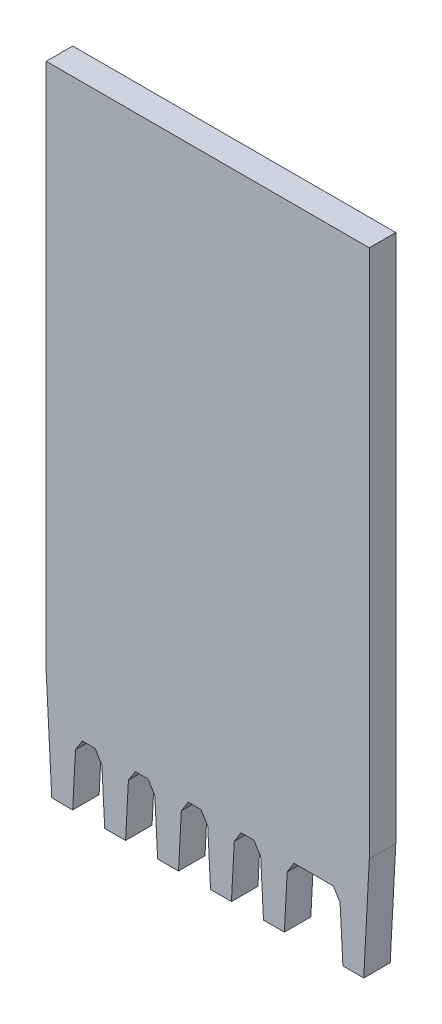
SolidWorks part; units mm, degrees
ref_plane "Front Plane" through (0, 0, 0) normal (0, 0, 1) x (1, 0, 0)
ref_plane "Top Plane" through (0, 0, 0) normal (0, 1, 0) x (1, 0, 0)
ref_plane "Right Plane" through (0, 0, 0) normal (1, 0, 0) x (0, 0, -1)
sketch "Sketch1" plane through (0, 0, 0) normal (0, 0, 1) x (1, 0, 0)
  line L0 (0, 0) -> (0, 36) construction
  line L1 (0, 36) -> (18.3124, 36) construction
  line L2 (18.3124, 36) -> (18.3124, 0) construction
  line L3 (18.3124, 0) -> (0, 0) construction
  line L4 (0, 3) -> (18.3124, 3) construction
  line L5 (0, 6) -> (18.3124, 6) construction
  line L6 (0.9062, 6) -> (0.9062, 0) construction
  line L7 (3.9062, 6) -> (3.9062, 0) construction
  line L8 (6.9062, 6) -> (6.9062, 0) construction
  line L9 (9.9062, 6) -> (9.9062, 0) construction
  line L10 (12.9062, 6) -> (12.9062, 0) construction
  line L11 (17.4062, 6) -> (17.4062, 0) construction
  line L12 (0.9062, 3) -> (3.9062, 3) construction
  line L13 (3.9062, 3) -> (6.9062, 3) construction
  line L14 (6.9062, 3) -> (9.9062, 3) construction
  line L15 (9.9062, 3) -> (12.9062, 3) construction
  line L16 (12.9062, 3) -> (17.4062, 3) construction
  line L17 (0.9062, 3) -> (0, 3) construction
  line L18 (17.4062, 3) -> (18.3124, 3) construction
  line L19 (2.4062, 3) -> (2.4062, 0) construction
  line L20 (5.4062, 3) -> (5.4062, 0) construction
  line L21 (8.4062, 3) -> (8.4062, 0) construction
  line L22 (11.4062, 3) -> (11.4062, 0) construction
  line L23 (15.1562, 3) -> (15.1562, 0) construction
  line L24 (14.4062, 3.75) -> (15.9062, 3.75) construction
  line L25 (0, 6) -> (0.3144, 0)
  line L26 (0.3144, 0) -> (1.4979, 0)
  line L27 (1.4979, 0) -> (1.6572, 3.0393)
  line L28 (3.1552, 3.0393) -> (3.3144, 0)
  line L29 (3.3144, 0) -> (4.4979, 0)
  line L30 (4.4979, 0) -> (4.6572, 3.0393)
  line L31 (6.1552, 3.0393) -> (6.3144, 0)
  line L32 (6.3144, 0) -> (7.4979, 0)
  line L33 (7.4979, 0) -> (7.6572, 3.0393)
  line L34 (9.1552, 3.0393) -> (9.3144, 0)
  line L35 (9.3144, 0) -> (10.4979, 0)
  line L36 (10.4979, 0) -> (10.6572, 3.0393)
  line L37 (12.1552, 3.0393) -> (12.3144, 0)
  line L38 (12.3144, 0) -> (13.4979, 0)
  line L39 (13.4979, 0) -> (13.6572, 3.0393)
  line L40 (16.6552, 3.0393) -> (16.8144, 0)
  line L41 (16.8144, 0) -> (17.9979, 0)
  line L42 (17.9979, 0) -> (18.3124, 6)
  line L44 (1.6572, 3.0393) -> (2.0426, 3.656)
  line L45 (0, 6) -> (0, 36)
  line L46 (0, 36) -> (18.3124, 36)
  line L47 (18.3124, 36) -> (18.3124, 6)
  line L48 (9.1562, 36) -> (9.1562, 6) construction
  line L49 (2.0426, 3.656) -> (2.7698, 3.656)
  line L50 (2.7698, 3.656) -> (3.1552, 3.0393)
  line L51 (4.6572, 3.0393) -> (5.0426, 3.656)
  line L52 (5.0426, 3.656) -> (5.7698, 3.656)
  line L53 (5.7698, 3.656) -> (6.1552, 3.0393)
  line L54 (7.6572, 3.0393) -> (8.0426, 3.656)
  line L55 (8.0426, 3.656) -> (8.7698, 3.656)
  line L56 (8.7698, 3.656) -> (9.1552, 3.0393)
  line L57 (10.6572, 3.0393) -> (11.0426, 3.656)
  line L58 (11.0426, 3.656) -> (11.7698, 3.656)
  line L59 (11.7698, 3.656) -> (12.1552, 3.0393)
  line L60 (13.6572, 3.0393) -> (14.0426, 3.656)
  line L61 (14.0426, 3.656) -> (16.2698, 3.656)
  line L62 (16.2698, 3.656) -> (16.6552, 3.0393)
  arc A0 (3.1552, 3.0393) -> (1.6572, 3.0393) centre (2.4062, 3) ccw construction
  arc A1 (6.1552, 3.0393) -> (4.6572, 3.0393) centre (5.4062, 3) ccw construction
  arc A2 (9.1552, 3.0393) -> (7.6572, 3.0393) centre (8.4062, 3) ccw construction
  arc A3 (12.1552, 3.0393) -> (10.6572, 3.0393) centre (11.4062, 3) ccw construction
  arc A4 (13.6572, 3.0393) -> (14.4062, 3.75) centre (14.4062, 3) cw construction
  arc A5 (16.6552, 3.0393) -> (15.9062, 3.75) centre (15.9062, 3) ccw construction
  dimension "D7" = 0.75
  dimension "D1" = 3
  dimension "D2" = 6
  dimension "D3" = 30
  dimension "D4" = 3
  dimension "D6" = 4.5
  dimension "D8" = 3
  dimension "D9" = 18.3124
  dimension "D10" = 36
extrude "Boss-Extrude1" add sketch "Sketch1" along normal blind 1.5
sketch "Sketch3" plane through (0, 0, 0) normal (0, 0, 1) x (1, 0, 0)
  line L0 (-0.4005, 6) -> (18.7129, 6)
  line L1 (18.7129, 3) -> (-0.4005, 3) construction
  line L2 (-0.4005, 0) -> (18.7129, 0) construction
  line L3 (-0.4005, -0.5) -> (18.7129, -0.5) construction
  line L4 (18.7129, -0.5) -> (18.7129, 6) construction
  line L5 (-0.4005, 6) -> (-0.4005, -0.5) construction
  line L6 (18.3124, 0) -> (0, 0) construction
  line L7 (0, 3) -> (18.3124, 3) construction
  line L8 (0, 6) -> (18.3124, 6) construction
  line L9 (0.3407, -0.5) -> (0, 6) construction
  line L10 (18.3124, 6) -> (17.9717, -0.5) construction
  line L11 (17.9979, 0) -> (18.3124, 6) construction
  line L12 (0, 6) -> (0.3144, 0) construction
  line L13 (5.4062, 6) -> (5.4062, -0.5) construction
  line L14 (3.9062, 6) -> (3.9062, -0.5) construction
  line L15 (5.4062, 3) -> (5.4062, 0) construction
  line L16 (3.1572, 3) -> (3.3407, -0.5) construction
  line L17 (2.7567, 3) -> (2.9401, -0.5)
  line L18 (3.1552, 3.0393) -> (3.3144, 0) construction
  line L19 (2.9401, -0.5) -> (4.8723, -0.5)
  line L20 (4.8723, -0.5) -> (5.0557, 3)
  line L21 (2.8484, 1.25) -> (3.2478, 1.2709) construction
  line L22 (5.9401, -0.5) -> (5.7567, 3)
  line L26 (7.8723, -0.5) -> (5.9401, -0.5)
  line L27 (8.0557, 3) -> (7.8723, -0.5)
  line L30 (2.4062, -0.5) -> (2.4062, 6) construction
  line L31 (2.4062, 3) -> (2.4062, 0) construction
  line L32 (8.4062, 6) -> (8.4062, -0.5) construction
  line L34 (11.4062, -0.5) -> (11.4062, 6) construction
  line L35 (15.1562, -0.5) -> (15.1562, 6) construction
  line L36 (8.4062, 3) -> (8.4062, 0) construction
  line L37 (11.4062, 3) -> (11.4062, 0) construction
  line L38 (15.1562, 3) -> (15.1562, 0) construction
  line L39 (10.8723, -0.5) -> (11.0557, 3)
  line L40 (8.9401, -0.5) -> (10.8723, -0.5)
  line L41 (8.7567, 3) -> (8.9401, -0.5)
  line L42 (11.9401, -0.5) -> (11.7567, 3)
  line L43 (13.8723, -0.5) -> (11.9401, -0.5)
  line L44 (14.0557, 3) -> (13.8723, -0.5)
  line L45 (16.4401, -0.5) -> (18.3723, -0.5)
  line L46 (16.2567, 3) -> (16.4401, -0.5)
  line L47 (18.3723, -0.5) -> (18.7129, 6)
  line L48 (1.8723, -0.5) -> (-0.0599, -0.5)
  line L49 (2.0557, 3) -> (1.8723, -0.5)
  line L50 (-0.0599, -0.5) -> (-0.4005, 6)
  line L51 (16.2567, 3) -> (14.0557, 3)
  line L52 (11.7567, 3) -> (11.0557, 3)
  line L53 (8.7567, 3) -> (8.0557, 3)
  line L54 (5.7567, 3) -> (5.0557, 3)
  line L55 (2.7567, 3) -> (2.0557, 3)
  dimension "D1" = 0.5
  dimension "D2" = 0.4
ref_plane "Plane1" through (3.9062, 0, 0) normal (1, 0, 0) x (0, 0, -1)
sketch "Sketch4" plane through (3.9062, 0, 0) normal (1, 0, 0) x (0, 0, -1)
  line L0 (0, 6) -> (0, -0.5) construction
  line L1 (0.6, 6) -> (-2.1, 6) construction
  line L2 (0.6, 6) -> (0.6, -0.5) construction
  line L3 (0.6, -0.5) -> (-2.1, -0.5) construction
  line L4 (-2.1, 6) -> (-2.1, -0.5) construction
  line L5 (-0.75, -0.5) -> (-0.75, 6) construction
  line L6 (-1.5, 6) -> (-1.5, -0.5) construction
  line L7 (0.6, 2.4005) -> (-2.1, 2.4005) construction
  line L8 (0.3, 6) -> (0.3, -0.5) construction
  line L9 (0.6, 2.4005) -> (3.846, 6) construction
  line L10 (2.2302, 6) -> (0.6, 4.1923) construction
  line L11 (0.6, 4.1923) -> (1.7139, 3.1878) construction
  line L12 (1.7139, 3.1878) -> (4.25, 6)
  line L13 (4.25, 6) -> (0.6, 6) construction
  line L14 (0.3, 1) -> (-1.8, 1) construction
  line L15 (-2.1, 0) -> (0.6, 0) construction
  line L16 (1.7139, 3.1878) -> (1.4912, 3.3887)
  line L17 (1.4912, 3.3887) -> (0.6, 2.4005)
  line L18 (-3.2139, 3.1878) -> (-5.75, 6)
  line L19 (-3.2139, 3.1878) -> (-2.9912, 3.3887)
  line L20 (-2.9912, 3.3887) -> (-2.1, 2.4005)
  line L21 (-2.1, 6) -> (-5.75, 6) construction
  line L22 (0.6, 3.0724) -> (3.2401, 6) construction
  arc A0 (0.4965, 2.2224) -> (0.6, -0.5) centre (4.2, 1) ccw
  arc A1 (0.6, 2.4005) -> (0.4965, 2.2224) centre (0.9713, 2.0656) ccw
  arc A2 (-2.1, 2.4005) -> (-1.9965, 2.2224) centre (-2.4713, 2.0656) cw
  arc A3 (-1.9965, 2.2224) -> (-2.1, -0.5) centre (-5.7, 1) cw
  dimension "D6" = 0.5
  dimension "D1" = 0.6
  dimension "D2" = 0.3
  dimension "D3" = 1.5
  dimension "D4" = 1
  dimension "D5" = 0.3
  dimension "D7" = 10
sketch "Sketch5" plane through (0, 0, 0) normal (1, 0, 0) x (0, 0, -1)
  line L0 (2.2302, 6) -> (0.6, 4.1923) construction
  line L1 (0.6, 4.1923) -> (1.7139, 3.1878) construction
  line L2 (1.7139, 3.1878) -> (4.25, 6) construction
  line L3 (2.2302, 6) -> (0.6, 4.1923) construction
  line L4 (0.6, 4.1923) -> (1.7139, 3.1878) construction
  line L5 (1.7139, 3.1878) -> (4.25, 6) construction
ref_plane "Plane2" through (0, 2.6105, -2.3541) normal (0, 0.7426, -0.6697) x (1, 0, 0)
sketch "Sketch6" plane through (0, 2.6105, -2.3541) normal (0, 0.7426, -0.6697) x (1, 0, 0)
  line L1 (3.9062, -2.362) -> (3.9062, -0.862) construction
  line L2 (3.9062, -2.362) -> (3.9062, -5.0612) construction
  line L3 (4.6562, -5.0612) -> (3.1562, -5.0612)
  line L4 (4.6562, -1.612) -> (3.1562, -1.612) construction
  line L5 (3.1562, -1.612) -> (3.1562, -5.0612)
  line L6 (4.6562, -1.612) -> (4.6562, -5.0612)
  line L10 (2.4062, -5.0612) -> (15.1562, -5.0612) construction
  line L11 (15.1562, -5.0612) -> (15.1562, -0.862) construction
  line L12 (15.1562, -0.862) -> (2.4062, -0.862) construction
  line L13 (2.4062, -0.862) -> (2.4062, -5.0612) construction
  line L14 (15.1562, 0.3349) -> (15.1562, -4.0182) construction
  line L15 (2.4062, 0.3349) -> (2.4062, -4.0182) construction
  line L16 (11.4062, -5.0612) -> (11.4062, -0.862) construction
  line L17 (8.4062, -5.0612) -> (8.4062, -0.862) construction
  line L18 (5.4062, -5.0612) -> (5.4062, -0.862) construction
  line L19 (5.4062, -4.0182) -> (5.4062, 0.3349) construction
  line L20 (8.4062, -4.0182) -> (8.4062, 0.3349) construction
  line L21 (11.4062, 0.3349) -> (11.4062, -4.0182) construction
  line L22 (0.1562, -1.612) -> (0.1562, -5.0612)
  line L23 (0.1562, -5.0612) -> (1.6562, -5.0612)
  line L24 (1.6562, -1.612) -> (1.6562, -5.0612)
  line L25 (7.6562, -1.612) -> (7.6562, -5.0612)
  line L26 (6.1562, -5.0612) -> (7.6562, -5.0612)
  line L27 (6.1562, -1.612) -> (6.1562, -5.0612)
  line L28 (10.6562, -1.612) -> (10.6562, -5.0612)
  line L29 (10.6562, -5.0612) -> (9.1562, -5.0612)
  line L30 (9.1562, -1.612) -> (9.1562, -5.0612)
  line L31 (13.6562, -1.612) -> (13.6562, -5.0612)
  line L32 (12.1562, -5.0612) -> (13.6562, -5.0612)
  line L33 (12.1562, -1.612) -> (12.1562, -5.0612)
  line L34 (18.1562, -1.612) -> (18.1562, -5.0612)
  line L35 (18.1562, -5.0612) -> (16.6562, -5.0612)
  line L36 (16.6562, -1.612) -> (16.6562, -5.0612)
  circle A0 centre (3.9062, -1.612) radius 0.75 construction
  arc A1 (4.6562, -1.612) -> (3.1562, -1.612) centre (3.9062, -1.612) ccw
  arc A2 (0.1562, -1.612) -> (1.6562, -1.612) centre (0.9062, -1.612) cw
  arc A3 (6.1562, -1.612) -> (7.6562, -1.612) centre (6.9062, -1.612) cw
  arc A4 (10.6562, -1.612) -> (9.1562, -1.612) centre (9.9062, -1.612) ccw
  arc A5 (12.1562, -1.612) -> (13.6562, -1.612) centre (12.9062, -1.612) cw
  arc A6 (18.1562, -1.612) -> (16.6562, -1.612) centre (17.4062, -1.612) ccw
ref_plane "Plane3" through (0, 1.6223, -1.463) normal (0, 0.7426, -0.6697) x (1, 0, 0)
sketch "Sketch7" plane through (0, 1.6223, -1.463) normal (0, 0.7426, -0.6697) x (1, 0, 0)
  line L0 (3.1562, -1.612) -> (3.1562, -5.0612) construction
  line L1 (4.6562, -5.0612) -> (3.1562, -5.0612) construction
  line L2 (4.6562, -1.612) -> (4.6562, -5.0612) construction
  line L3 (3.1562, -1.612) -> (3.1562, -5.0612) construction
  line L4 (4.6562, -5.0612) -> (3.1562, -5.0612) construction
  line L5 (4.6562, -1.612) -> (4.6562, -5.0612) construction
  line L6 (3.9062, -0.862) -> (3.9062, -5.0612) construction
  line L7 (4.6562, -1.612) -> (3.1562, -1.612) construction
  line L8 (4.6562, -2.362) -> (3.1562, -2.362) construction
  line L9 (3.4562, -1.612) -> (3.4562, -2.362)
  line L10 (3.4562, -2.362) -> (4.3562, -2.362)
  line L11 (4.3562, -2.362) -> (4.3562, -1.612)
  line L12 (2.4062, -0.862) -> (2.4062, -5.0612) construction
  line L13 (2.4062, -5.0612) -> (15.1562, -5.0612) construction
  line L14 (15.1562, -0.862) -> (2.4062, -0.862) construction
  line L15 (5.4062, -5.0612) -> (5.4062, -0.862) construction
  line L16 (8.4062, -5.0612) -> (8.4062, -0.862) construction
  line L17 (11.4062, -5.0612) -> (11.4062, -0.862) construction
  line L18 (15.1562, -5.0612) -> (15.1562, -0.862) construction
  line L19 (2.4062, -0.862) -> (2.4062, -5.0612) construction
  line L20 (2.4062, -5.0612) -> (15.1562, -5.0612) construction
  line L21 (15.1562, -0.862) -> (2.4062, -0.862) construction
  line L22 (5.4062, -5.0612) -> (5.4062, -0.862) construction
  line L23 (8.4062, -5.0612) -> (8.4062, -0.862) construction
  line L24 (11.4062, -5.0612) -> (11.4062, -0.862) construction
  line L25 (15.1562, -5.0612) -> (15.1562, -0.862) construction
  line L26 (0.4562, -2.362) -> (0.4562, -1.612)
  line L27 (1.3562, -2.362) -> (0.4562, -2.362)
  line L28 (1.3562, -1.612) -> (1.3562, -2.362)
  line L29 (7.3562, -2.362) -> (6.4562, -2.362)
  line L30 (7.3562, -1.612) -> (7.3562, -2.362)
  line L31 (6.4562, -2.362) -> (6.4562, -1.612)
  line L32 (9.4562, -1.612) -> (9.4562, -2.362)
  line L33 (10.3562, -2.362) -> (10.3562, -1.612)
  line L34 (9.4562, -2.362) -> (10.3562, -2.362)
  line L35 (13.3562, -1.612) -> (13.3562, -2.362)
  line L36 (12.4562, -2.362) -> (12.4562, -1.612)
  line L37 (13.3562, -2.362) -> (12.4562, -2.362)
  line L38 (16.9562, -1.612) -> (16.9562, -2.362)
  line L39 (17.8562, -2.362) -> (17.8562, -1.612)
  line L40 (16.9562, -2.362) -> (17.8562, -2.362)
  arc A0 (4.6562, -1.612) -> (3.1562, -1.612) centre (3.9062, -1.612) ccw construction
  arc A1 (4.6562, -1.612) -> (3.1562, -1.612) centre (3.9062, -1.612) ccw construction
  circle A2 centre (3.9062, -1.612) radius 0.45 construction
  arc A3 (4.3562, -1.612) -> (3.4562, -1.612) centre (3.9062, -1.612) ccw
  arc A4 (0.4562, -1.612) -> (1.3562, -1.612) centre (0.9062, -1.612) cw
  arc A5 (6.4562, -1.612) -> (7.3562, -1.612) centre (6.9062, -1.612) cw
  arc A6 (10.3562, -1.612) -> (9.4562, -1.612) centre (9.9062, -1.612) ccw
  arc A7 (12.4562, -1.612) -> (13.3562, -1.612) centre (12.9062, -1.612) cw
  arc A8 (17.8562, -1.612) -> (16.9562, -1.612) centre (17.4062, -1.612) ccw
ref_plane "bisect" through (0, 0, 0.75) normal (0, 0, 1) x (1, 0, 0)
ref_plane "insert_surface" through (0, 6, 0) normal (0, 1, 0) x (1, 0, 0)
sketch "Sketch8" plane through (0, 6, 0) normal (0, 1, 0) x (1, 0, 0)
  line L0 (18.7129, -0.75) -> (-0.4005, -0.75) construction
  line L1 (-0.4005, 0.6) -> (18.7129, 0.6)
  line L2 (-0.4005, 0.6) -> (-0.4005, -2.1)
  line L3 (-0.4005, -2.1) -> (18.7129, -2.1)
  line L4 (18.7129, 0.6) -> (18.7129, -2.1)
  line L5 (9.1562, 0.6) -> (9.1562, -2.1) construction
  line L6 (0, 0) -> (18.3124, 0) construction
  line L7 (0, 0) -> (0, -1.5) construction
  line L8 (0, -1.5) -> (18.3124, -1.5) construction
  line L9 (18.3124, 0) -> (18.3124, -1.5) construction
  line L10 (18.7129, 0.3) -> (-0.4005, 0.3) construction
  line L11 (18.7129, -1.8) -> (-0.4005, -1.8) construction
sketch "Sketch9" plane through (0, 0, 0) normal (0, 0, 1) x (1, 0, 0)
  line L0 (18.3723, -0.5) -> (18.7129, 6) construction
  line L1 (-0.4005, 6) -> (18.7129, 6) construction
  line L2 (-0.0599, -0.5) -> (-0.4005, 6) construction
  line L3 (1.8723, -0.5) -> (-0.0599, -0.5) construction
  line L4 (2.0557, 3) -> (1.8723, -0.5) construction
  line L5 (2.7567, 3) -> (2.0557, 3) construction
  line L6 (2.7567, 3) -> (2.9401, -0.5) construction
  line L7 (2.9401, -0.5) -> (4.8723, -0.5) construction
  line L8 (4.8723, -0.5) -> (5.0557, 3) construction
  line L9 (5.7567, 3) -> (5.0557, 3) construction
  line L10 (5.9401, -0.5) -> (5.7567, 3) construction
  line L11 (7.8723, -0.5) -> (5.9401, -0.5) construction
  line L12 (8.0557, 3) -> (7.8723, -0.5) construction
  line L13 (8.7567, 3) -> (8.0557, 3) construction
  line L14 (8.7567, 3) -> (8.9401, -0.5) construction
  line L15 (8.9401, -0.5) -> (10.8723, -0.5) construction
  line L16 (10.8723, -0.5) -> (11.0557, 3) construction
  line L17 (11.7567, 3) -> (11.0557, 3) construction
  line L18 (11.9401, -0.5) -> (11.7567, 3) construction
  line L19 (13.8723, -0.5) -> (11.9401, -0.5) construction
  line L20 (14.0557, 3) -> (13.8723, -0.5) construction
  line L21 (16.2567, 3) -> (14.0557, 3) construction
  line L22 (16.2567, 3) -> (16.4401, -0.5) construction
  line L23 (16.4401, -0.5) -> (18.3723, -0.5) construction
  line L24 (18.3723, -0.5) -> (18.7129, 6)
  line L25 (-0.4005, 6) -> (18.7129, 6) construction
  line L26 (-0.0599, -0.5) -> (-0.4005, 6)
  line L27 (1.8723, -0.5) -> (-0.0599, -0.5)
  line L28 (2.0557, 3) -> (1.8723, -0.5)
  line L29 (2.7567, 3) -> (2.0557, 3) construction
  line L30 (2.7567, 3) -> (2.9401, -0.5)
  line L31 (2.9401, -0.5) -> (4.8723, -0.5)
  line L32 (4.8723, -0.5) -> (5.0557, 3)
  line L33 (5.7567, 3) -> (5.0557, 3) construction
  line L34 (5.9401, -0.5) -> (5.7567, 3)
  line L35 (7.8723, -0.5) -> (5.9401, -0.5)
  line L36 (8.0557, 3) -> (7.8723, -0.5)
  line L37 (8.7567, 3) -> (8.0557, 3) construction
  line L38 (8.7567, 3) -> (8.9401, -0.5)
  line L39 (8.9401, -0.5) -> (10.8723, -0.5)
  line L40 (10.8723, -0.5) -> (11.0557, 3)
  line L41 (11.7567, 3) -> (11.0557, 3) construction
  line L42 (11.9401, -0.5) -> (11.7567, 3)
  line L43 (13.8723, -0.5) -> (11.9401, -0.5)
  line L44 (14.0557, 3) -> (13.8723, -0.5)
  line L45 (16.2567, 3) -> (14.0557, 3) construction
  line L46 (16.2567, 3) -> (16.4401, -0.5)
  line L47 (16.4401, -0.5) -> (18.3723, -0.5)
  line L48 (16.2567, 3) -> (16.2567, 6)
  line L49 (14.0557, 3) -> (14.0557, 6)
  line L50 (11.7567, 3) -> (11.7567, 6)
  line L51 (18.7129, 6) -> (-0.4005, 6) construction
  line L52 (11.0557, 3) -> (11.0557, 6)
  line L53 (-0.4005, 6) -> (18.7129, 6) construction
  line L54 (8.7567, 3) -> (8.7567, 6)
  line L55 (8.0557, 3) -> (8.0557, 6)
  line L58 (5.7567, 3) -> (5.7567, 6)
  line L60 (5.0557, 3) -> (5.0557, 6)
  line L62 (15.1562, -0.5) -> (15.1562, 6) construction
  line L63 (15.1562, -0.5) -> (15.1562, 6) construction
  line L64 (2.7567, 3) -> (2.7567, 6)
  line L65 (2.0557, 3) -> (2.0557, 6)
  line L67 (18.7129, 6) -> (16.2567, 6)
  line L68 (14.0557, 6) -> (11.7567, 6)
  line L69 (11.0557, 6) -> (8.7567, 6)
  line L70 (8.0557, 6) -> (5.7567, 6)
  line L71 (5.0557, 6) -> (2.7567, 6)
  line L72 (2.0557, 6) -> (-0.4005, 6)
